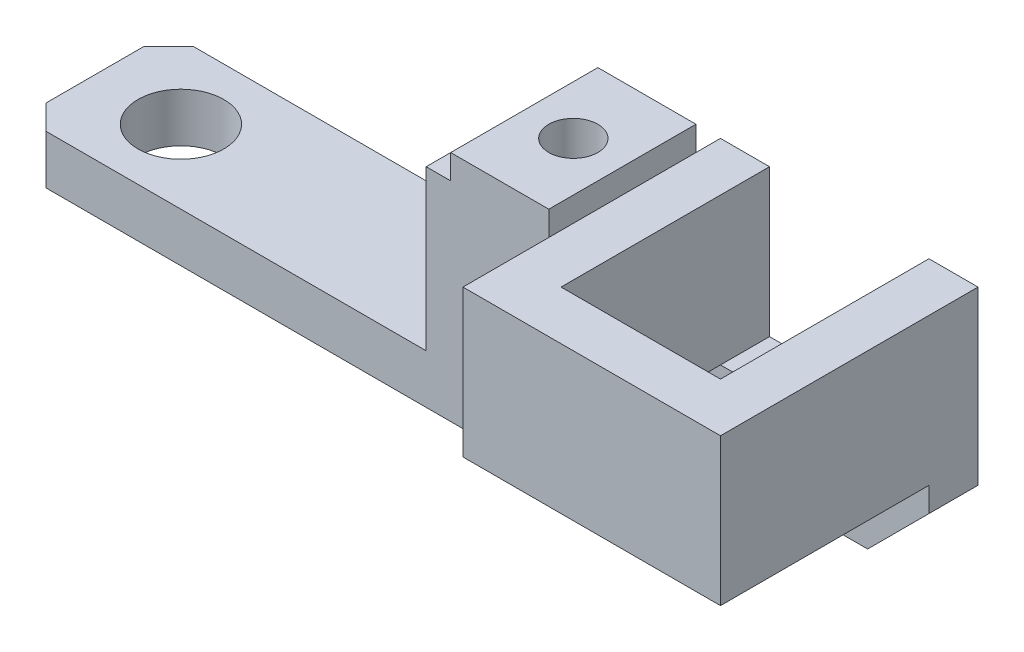
SolidWorks part; units mm, degrees
ref_plane "前视基准面" through (0, 0, 0) normal (0, 0, 1) x (1, 0, 0)
ref_plane "上视基准面" through (0, 0, 0) normal (0, 1, 0) x (1, 0, 0)
ref_plane "右视基准面" through (0, 0, 0) normal (1, 0, 0) x (0, 0, -1)
sketch "草图1" plane through (0, 0, 0) normal (0, 1, 0) x (1, 0, 0)
  line L1 (-16.5, -6) -> (16.5, -6)
  line L2 (-16.5, -6) -> (-16.5, 6)
  line L3 (-16.5, 6) -> (16.5, 6)
  line L4 (16.5, -6) -> (16.5, 6)
  line L5 (-16.5, -6) -> (16.5, 6) construction
  line L6 (-16.5, 6) -> (16.5, -6) construction
  line L7 (28.5, -6) -> (16.5, -6)
  line L8 (28.5, -6) -> (28.5, 6)
  line L9 (28.5, 6) -> (16.5, 6)
  line L10 (16.5, -6) -> (16.5, 6)
  line L11 (28.5, -6) -> (16.5, 6) construction
  line L12 (28.5, 6) -> (16.5, -6) construction
  point P0 (0, 0)
  point P5 (22.5, 0)
  dimension "D1" = 33
  dimension "D2" = 12
  dimension "D3" = 45
extrude "凸台-拉伸1" add sketch "草图1" along normal blind 4 contours L1 L4 L3 L2 region at (0, 0, 0)
extrude "凸台-拉伸2" add sketch "草图1<3>" along normal blind 19 contours L10 L7 L8 L9
sketch "草图1<3>" plane through (0, 0, 0) normal (0, 1, 0) x (1, 0, 0) same geometry as "草图1"
sketch "草图2" plane through (0, 19, 0) normal (0, 1, 0) x (1, 0, 0)
  line L0 (18.5, 6) -> (18.5, -6)
  line L1 (26.5, 6) -> (26.5, -6)
  line L4 (28.5, 6) -> (16.5, 6)
  line L5 (16.5, 6) -> (16.5, -6)
  line L6 (16.5, -6) -> (28.5, -6)
  line L7 (28.5, -6) -> (28.5, 6)
  line L8 (28.5, 6) -> (16.5, 6)
  line L9 (16.5, 6) -> (16.5, -6)
  line L10 (16.5, -6) -> (28.5, -6)
  line L11 (28.5, -6) -> (28.5, 6)
  line M7 (28.5, 6) -> (16.5, 6)
  line M8 (16.5, 6) -> (16.5, -6)
  line M9 (16.5, -6) -> (28.5, -6)
  line M10 (28.5, -6) -> (28.5, 6)
  dimension "D2" = 2
  dimension "D3" = 2
  dimension "D1" = 0
extrude "切除-拉伸1" cut sketch "草图2" against normal blind 2 contours L0 M7 M8 M9 | L1 M7 M9 M10 region at (17.5, 19, 0) region at (27.5, 19, 0)
sketch "草图3" plane through (0, 0, 0) normal (0, -1, 0) x (1, 0, 0)
  line L5 (49.5, 15) -> (28.5, 15)
  line L6 (49.5, 15) -> (49.5, -6)
  line L7 (49.5, -6) -> (28.5, -6)
  line L8 (28.5, 15) -> (28.5, -6)
  line L9 (49.5, 15) -> (28.5, -6) construction
  line L10 (49.5, -6) -> (28.5, 15) construction
  point P0 (39, 4.5)
  dimension "D1" = 21
extrude "凸台-拉伸3" add sketch "草图3" against normal blind 19
sketch "草图4" plane through (0, 0, 15) normal (0, 0, 1) x (1, 0, 0)
  line L0 (49.5, 5) -> (44.5, 0)
  line L1 (49.5, 19) -> (49.5, 0) construction
  line L2 (49.5, 0) -> (28.5, 0) construction
  line L3 (44.5, 0) -> (49.5, 0)
  line L4 (49.5, 0) -> (49.5, 5)
  dimension "D1" = 5
extrude "切除-拉伸2" cut sketch "草图4" against normal through all
sketch "草图5" plane through (0, 19, 0) normal (0, 1, 0) x (1, 0, 0)
  line L0 (49.5, 6) -> (28.5, -15) construction
  line L1 (49.5, -15) -> (28.5, -15) construction
  line L2 (32.5, 2) -> (45.5, 2)
  line L3 (32.5, 2) -> (32.5, -11)
  line L4 (32.5, -11) -> (45.5, -11)
  line L5 (45.5, 2) -> (45.5, -11)
  line L6 (32.5, 2) -> (45.5, -11) construction
  line L7 (32.5, -11) -> (45.5, 2) construction
  line L8 (49.5, 6) -> (49.5, -15) construction
  point P4 (39, -4.5)
  point P9 (0, 0)
  dimension "D1" = 4
  dimension "D2" = 4
extrude "切除-拉伸3" cut sketch "草图5" against normal through all
sketch "草图6" plane through (0, 19, 0) normal (0, 1, 0) x (1, 0, 0)
  line L0 (28.5, 6) -> (49.5, 6) construction
  line L1 (32.5, 2) -> (45.5, 2)
  line L2 (32.5, 2) -> (32.5, 6)
  line L3 (32.5, 6) -> (45.5, 6)
  line L4 (45.5, 2) -> (45.5, 6)
  line L5 (45.5, -11) -> (45.5, 2) construction
extrude "切除-拉伸4" cut sketch "草图6" against normal offset from surface (12 mm away) 7 up to face at (26.7, 0, 4.8)
sketch "草图7" plane through (0, 0, 15) normal (0, 0, 1) x (1, 0, 0)
  line L0 (49.5, 19) -> (49.5, 5) construction
  line L1 (28.5, 0) -> (49.5, 0)
  line L2 (28.5, 0) -> (28.5, 7)
  line L3 (28.5, 7) -> (49.5, 7)
  line L4 (49.5, 0) -> (49.5, 7)
  dimension "D1" = 7
extrude "切除-拉伸5" cut sketch "草图7" against normal up to surface (17 mm away) up to face at (40.1, 3, -2)
sketch "草图8" plane through (0, 4, 0) normal (0, 1, 0) x (1, 0, 0)
  line L0 (-9.5, 0) -> (0, 0) construction
  line L1 (-16.5, -6) -> (-16.5, 6) construction
  circle A0 centre (-9.5, 0) radius 3.5
  dimension "D1" = 7
  dimension "D2" = 7
extrude "切除-拉伸6" cut sketch "草图8" against normal through all both and the other way through all
sketch "草图9" plane through (0, 19, 0) normal (0, 1, 0) x (1, 0, 0)
  line L0 (22.5, 6) -> (22.5, -6) construction
  line L1 (26.5, 6) -> (18.5, 6) construction
  line L2 (26.5, -6) -> (18.5, -6) construction
  circle A0 centre (22.5, 0) radius 2
  point P8 (0, 0)
  dimension "D1" = 4
extrude "切除-拉伸7" cut sketch "草图9" against normal through all both and the other way through all
chamfer "倒角1" distance 2 angle 45 2 edges at (-16.5, 2, -6) (-16.5, 2, 6)
